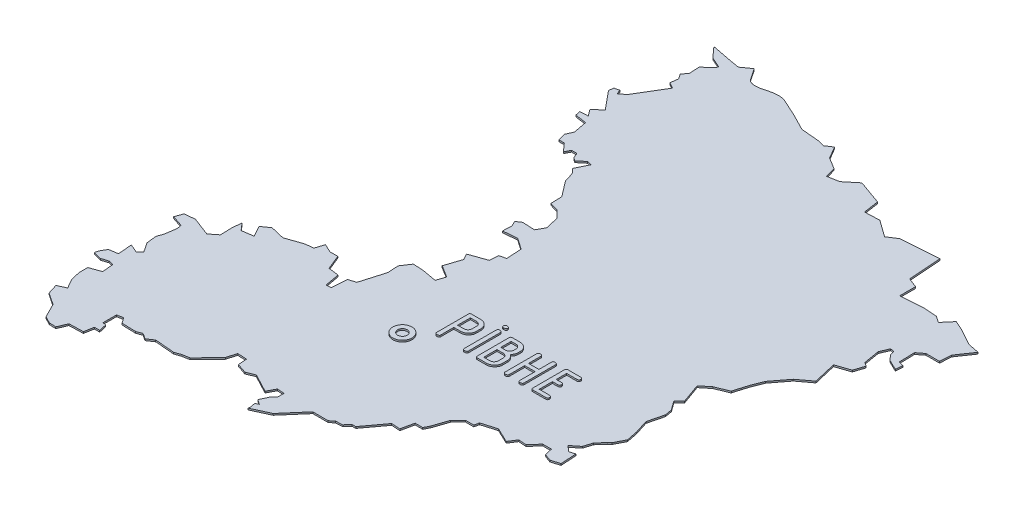
SolidWorks part; units mm, degrees
ref_plane "Спереди" through (0, 0, 0) normal (0, 0, 1) x (1, 0, 0)
ref_plane "Сверху" through (0, 0, 0) normal (0, 1, 0) x (1, 0, 0)
ref_plane "Справа" through (0, 0, 0) normal (1, 0, 0) x (0, 0, -1)
sketch "Эскиз1" plane through (0, 0, 0) normal (0, 1, 0) x (1, 0, 0)
  line B0 (-6710.873, 8600.8413) -> (-6732.9329, 8609.2792)
  line B1 (-6732.9329, 8609.2792) -> (-6738.1349, 8633.2797)
  line B2 (-6738.1349, 8633.2797) -> (-6765.3713, 8633.2797)
  line B3 (-6765.3713, 8633.2797) -> (-6790.6824, 8605.3676)
  line B4 (-6790.6824, 8605.3676) -> (-6814.6905, 8607.3209)
  line B5 (-6814.6905, 8607.3209) -> (-6830.2657, 8583.3077)
  line B6 (-6830.2657, 8583.3077) -> (-6876.3642, 8605.3676)
  line B7 (-6876.3642, 8605.3676) -> (-6922.4068, 8591.7481)
  line B8 (-6922.4068, 8591.7481) -> (-6925.6554, 8576.8332)
  line B9 (-6925.6554, 8576.8332) -> (-6951.6168, 8576.8332)
  line B10 (-6951.6168, 8576.8332) -> (-6974.9772, 8552.8125)
  line B11 (-6974.9772, 8552.8125) -> (-6990.5651, 8506.7419)
  line B12 (-6990.5651, 8506.7419) -> (-6999.003, 8489.8738)
  line B13 (-6999.003, 8489.8738) -> (-7023.0086, 8489.8738)
  line B14 (-7023.0086, 8489.8738) -> (-7031.4541, 8450.265)
  line B15 (-7031.4541, 8450.265) -> (-7058.6879, 8452.2132)
  line B16 (-7058.6879, 8452.2132) -> (-7106.7066, 8387.3365)
  line B17 (-7106.7066, 8387.3365) -> (-7118.411, 8387.3365)
  line B18 (-7118.411, 8387.3365) -> (-7132.0228, 8371.7587)
  line B19 (-7132.0228, 8371.7587) -> (-7152.7848, 8370.4735)
  line B20 (-7152.7848, 8370.4735) -> (-7166.4271, 8360.0722)
  line B21 (-7166.4271, 8360.0722) -> (-7214.4585, 8360.0722)
  line B22 (-7214.4585, 8360.0722) -> (-7272.1902, 8293.2372)
  line B23 (-7272.1902, 8293.2372) -> (-7326.0661, 8268.5788)
  line B24 (-7326.0661, 8268.5788) -> (-7324.758, 8276.3563)
  line B25 (-7324.758, 8276.3563) -> (-7328.6518, 8291.9418)
  line B26 (-7328.6518, 8291.9418) -> (-7318.2785, 8296.4706)
  line B27 (-7318.2785, 8296.4706) -> (-7333.8487, 8306.8668)
  line B28 (-7333.8487, 8306.8668) -> (-7320.2165, 8336.0844)
  line B29 (-7320.2165, 8336.0844) -> (-7309.8482, 8346.4578)
  line B30 (-7309.8482, 8346.4578) -> (-7309.8482, 8365.2665)
  line B31 (-7309.8482, 8365.2665) -> (-7331.8954, 8366.5746)
  line B32 (-7331.8954, 8366.5746) -> (-7345.5352, 8341.2584)
  line B33 (-7345.5352, 8341.2584) -> (-7403.2821, 8371.7587)
  line B34 (-7403.2821, 8371.7587) -> (-7429.2536, 8361.3803)
  line B35 (-7429.2536, 8361.3803) -> (-7459.7438, 8371.7587)
  line B36 (-7459.7438, 8371.7587) -> (-7461.692, 8399.0231)
  line B37 (-7461.692, 8399.0231) -> (-7490.9045, 8400.9611)
  line B38 (-7490.9045, 8400.9611) -> (-7499.3398, 8370.4735)
  line B39 (-7499.3398, 8370.4735) -> (-7553.8432, 8314.0067)
  line B40 (-7553.8432, 8314.0067) -> (-7575.9081, 8310.118)
  line B41 (-7575.9081, 8310.118) -> (-7594.7219, 8303.6232)
  line B42 (-7594.7219, 8303.6232) -> (-7656.3728, 8308.8099)
  line B43 (-7656.3728, 8308.8099) -> (-7676.4947, 8295.1828)
  line B44 (-7676.4947, 8295.1828) -> (-7694.0181, 8306.8668)
  line B45 (-7694.0181, 8306.8668) -> (-7710.8964, 8300.372)
  line B46 (-7710.8964, 8300.372) -> (-7755.0137, 8301.6725)
  line B47 (-7755.0137, 8301.6725) -> (-7767.3479, 8319.1858)
  line B48 (-7767.3479, 8319.1858) -> (-7786.1643, 8315.3098)
  line B49 (-7786.1643, 8315.3098) -> (-7786.1643, 8273.1153)
  line B50 (-7786.1643, 8273.1153) -> (-7775.7655, 8271.1773)
  line B51 (-7775.7655, 8271.1773) -> (-7770.5941, 8247.1743)
  line B52 (-7770.5941, 8247.1743) -> (-7787.447, 8247.1743)
  line B53 (-7787.447, 8247.1743) -> (-7792.6463, 8217.9592)
  line B54 (-7792.6463, 8217.9592) -> (-7836.7687, 8216.6663)
  line B55 (-7836.7687, 8216.6663) -> (-7849.1004, 8187.4563)
  line B56 (-7849.1004, 8187.4563) -> (-7870.5075, 8188.7593)
  line B57 (-7870.5075, 8188.7593) -> (-7891.9426, 8199.7855)
  line B58 (-7891.9426, 8199.7855) -> (-7914.0101, 8243.9231)
  line B59 (-7914.0101, 8243.9231) -> (-7951.6249, 8269.2265)
  line B60 (-7951.6249, 8269.2265) -> (-7961.3735, 8300.372)
  line B61 (-7961.3735, 8300.372) -> (-7936.0497, 8312.0459)
  line B62 (-7936.0497, 8312.0459) -> (-7952.928, 8341.2584)
  line B63 (-7952.928, 8341.2584) -> (-7960.073, 8371.7587)
  line B64 (-7960.073, 8371.7587) -> (-7960.073, 8399.0231)
  line B65 (-7960.073, 8399.0231) -> (-7925.6763, 8411.337)
  line B66 (-7925.6763, 8411.337) -> (-7928.9224, 8447.0418)
  line B67 (-7928.9224, 8447.0418) -> (-7944.5028, 8450.265)
  line B68 (-7944.5028, 8450.265) -> (-7965.2622, 8443.7982)
  line B69 (-7965.2622, 8443.7982) -> (-7990.5708, 8450.265)
  line B70 (-7990.5708, 8450.265) -> (-7987.3348, 8462.6044)
  line B71 (-7987.3348, 8462.6044) -> (-7976.936, 8480.7781)
  line B72 (-7976.936, 8480.7781) -> (-7949.6869, 8484.6897)
  line B73 (-7949.6869, 8484.6897) -> (-7952.928, 8528.8069)
  line B74 (-7952.928, 8528.8069) -> (-7925.6763, 8517.1229)
  line B75 (-7925.6763, 8517.1229) -> (-7914.0101, 8528.8069)
  line B76 (-7914.0101, 8528.8069) -> (-7934.1193, 8559.292)
  line B77 (-7934.1193, 8559.292) -> (-7938.0004, 8590.4476)
  line B78 (-7938.0004, 8590.4476) -> (-7930.8731, 8610.5695)
  line B79 (-7930.8731, 8610.5695) -> (-7925.6763, 8646.9068)
  line B80 (-7925.6763, 8646.9068) -> (-7928.9224, 8660.5364)
  line B81 (-7928.9224, 8660.5364) -> (-7963.3369, 8672.2331)
  line B82 (-7963.3369, 8672.2331) -> (-7954.8812, 8696.2209)
  line B83 (-7954.8812, 8696.2209) -> (-7922.42, 8699.4721)
  line B84 (-7922.42, 8699.4721) -> (-7864.6757, 8677.402)
  line B85 (-7864.6757, 8677.402) -> (-7840.665, 8696.2209)
  line B86 (-7840.665, 8696.2209) -> (-7841.9579, 8735.1692)
  line B87 (-7841.9579, 8735.1692) -> (-7838.727, 8762.4056)
  line B88 (-7838.727, 8762.4056) -> (-7819.9082, 8740.3635)
  line B89 (-7819.9082, 8740.3635) -> (-7784.2059, 8745.54)
  line B90 (-7784.2059, 8745.54) -> (-7803.0324, 8779.9342)
  line B91 (-7803.0324, 8779.9342) -> (-7779.0294, 8796.8049)
  line B92 (-7779.0294, 8796.8049) -> (-7734.8918, 8786.434)
  line B93 (-7734.8918, 8786.434) -> (-7683.6168, 8803.9372)
  line B94 (-7683.6168, 8803.9372) -> (-7657.6682, 8807.2036)
  line B95 (-7657.6682, 8807.2036) -> (-7649.2278, 8834.4527)
  line B96 (-7649.2278, 8834.4527) -> (-7621.9837, 8822.1109)
  line B97 (-7621.9837, 8822.1109) -> (-7597.9807, 8822.1109)
  line B98 (-7597.9807, 8822.1109) -> (-7579.1416, 8776.0429)
  line B99 (-7579.1416, 8776.0429) -> (-7546.6981, 8771.5014)
  line B100 (-7546.6981, 8771.5014) -> (-7538.2679, 8725.4309)
  line B101 (-7538.2679, 8725.4309) -> (-7523.3352, 8726.7085)
  line B102 (-7523.3352, 8726.7085) -> (-7519.4439, 8774.7399)
  line B103 (-7519.4439, 8774.7399) -> (-7497.3891, 8781.2372)
  line B104 (-7497.3891, 8781.2372) -> (-7475.3114, 8856.505)
  line B105 (-7475.3114, 8856.505) -> (-7477.2622, 8890.9042)
  line B106 (-7477.2622, 8890.9042) -> (-7458.4535, 8919.4665)
  line B107 (-7458.4535, 8919.4665) -> (-7427.2877, 8918.1661)
  line B108 (-7427.2877, 8918.1661) -> (-7379.9167, 8909.718)
  line B109 (-7379.9167, 8909.718) -> (-7370.8336, 8936.9798)
  line B110 (-7370.8336, 8936.9798) -> (-7408.4866, 8960.3529)
  line B111 (-7408.4866, 8960.3529) -> (-7391.6032, 9011.6127)
  line B112 (-7391.6032, 9011.6127) -> (-7401.9867, 9030.4264)
  line B113 (-7401.9867, 9030.4264) -> (-7348.7737, 9049.2605)
  line B114 (-7348.7737, 9049.2605) -> (-7347.4656, 9076.5097)
  line B115 (-7347.4656, 9076.5097) -> (-7326.7011, 9081.6913)
  line B116 (-7326.7011, 9081.6913) -> (-7329.9574, 9129.71)
  line B117 (-7329.9574, 9129.71) -> (-7364.3541, 9153.7257)
  line B118 (-7364.3541, 9153.7257) -> (-7408.4866, 9149.8318)
  line B119 (-7408.4866, 9149.8318) -> (-7407.1785, 9179.0317)
  line B120 (-7407.1785, 9179.0317) -> (-7415.6138, 9194.6171)
  line B121 (-7415.6138, 9194.6171) -> (-7400.0385, 9204.9854)
  line B122 (-7400.0385, 9204.9854) -> (-7361.113, 9203.0347)
  line B123 (-7361.113, 9203.0347) -> (-7347.4656, 9228.3534)
  line B124 (-7347.4656, 9228.3534) -> (-7357.2091, 9269.2499)
  line B125 (-7357.2091, 9269.2499) -> (-7381.2121, 9293.2529)
  line B126 (-7381.2121, 9293.2529) -> (-7407.1785, 9300.3802)
  line B127 (-7407.1785, 9300.3802) -> (-7408.4866, 9336.0875)
  line B128 (-7408.4866, 9336.0875) -> (-7446.0938, 9385.3965)
  line B129 (-7446.0938, 9385.3965) -> (-7454.5546, 9414.6065)
  line B130 (-7454.5546, 9414.6065) -> (-7468.1893, 9430.1589)
  line B131 (-7468.1893, 9430.1589) -> (-7449.3755, 9469.1175)
  line B132 (-7449.3755, 9469.1175) -> (-7463.63, 9472.3636)
  line B133 (-7463.63, 9472.3636) -> (-7485.6924, 9454.1848)
  line B134 (-7485.6924, 9454.1848) -> (-7495.4384, 9460.672)
  line B135 (-7495.4384, 9460.672) -> (-7502.5783, 9477.5401)
  line B136 (-7502.5783, 9477.5401) -> (-7519.4439, 9477.5401)
  line B137 (-7519.4439, 9477.5401) -> (-7527.8844, 9460.672)
  line B138 (-7527.8844, 9460.672) -> (-7550.6021, 9485.9805)
  line B139 (-7550.6021, 9485.9805) -> (-7567.4576, 9485.9805)
  line B140 (-7567.4576, 9485.9805) -> (-7573.9549, 9509.9911)
  line B141 (-7573.9549, 9509.9911) -> (-7564.2216, 9532.0587)
  line B142 (-7564.2216, 9532.0587) -> (-7572.662, 9574.8932)
  line B143 (-7572.662, 9574.8932) -> (-7608.3465, 9580.0875)
  line B144 (-7608.3465, 9580.0875) -> (-7611.5977, 9595.645)
  line B145 (-7611.5977, 9595.645) -> (-7586.2866, 9596.9455)
  line B146 (-7586.2866, 9596.9455) -> (-7601.8619, 9617.7278)
  line B147 (-7601.8619, 9617.7278) -> (-7575.9081, 9639.7877)
  line B148 (-7575.9081, 9639.7877) -> (-7623.9395, 9698.1848)
  line B149 (-7623.9395, 9698.1848) -> (-7621.9837, 9713.1048)
  line B150 (-7621.9837, 9713.1048) -> (-7606.3983, 9716.9935)
  line B151 (-7606.3983, 9716.9935) -> (-7601.8619, 9702.7213)
  line B152 (-7601.8619, 9702.7213) -> (-7583.0303, 9716.9935)
  line B153 (-7583.0303, 9716.9935) -> (-7529.8325, 9805.2636)
  line B154 (-7529.8325, 9805.2636) -> (-7548.6489, 9815.642)
  line B155 (-7548.6489, 9815.642) -> (-7545.39, 9839.6501)
  line B156 (-7545.39, 9839.6501) -> (-7555.7863, 9855.2305)
  line B157 (-7555.7863, 9855.2305) -> (-7543.4469, 9872.0885)
  line B158 (-7543.4469, 9872.0885) -> (-7545.39, 9904.5395)
  line B159 (-7545.39, 9904.5395) -> (-7524.6433, 9921.4203)
  line B160 (-7524.6433, 9921.4203) -> (-7514.2395, 9935.0525)
  line B161 (-7514.2395, 9935.0525) -> (-7548.6489, 9950.6329)
  line B162 (-7548.6489, 9950.6329) -> (-7577.8538, 9983.0712)
  line B163 (-7577.8538, 9983.0712) -> (-7514.2395, 9970.7294)
  line B164 (-7514.2395, 9970.7294) -> (-7483.7646, 9965.5401)
  line B165 (-7483.7646, 9965.5401) -> (-7454.5546, 9986.3123)
  line B166 (-7454.5546, 9986.3123) -> (-7429.2536, 9948.6898)
  line B167 (-7323.455, 9948.6898) -> (-7270.2522, 9924.6665)
  line B168 (-7270.2522, 9924.6665) -> (-7214.4585, 9896.1118)
  line B169 (-7214.4585, 9896.1118) -> (-7156.0385, 9890.9276)
  line B170 (-7156.0385, 9890.9276) -> (-7135.9243, 9885.7257)
  line B171 (-7135.9243, 9885.7257) -> (-7115.1648, 9899.3808)
  line B172 (-7115.1648, 9899.3808) -> (-7093.0872, 9861.7227)
  line B173 (-7093.0872, 9861.7227) -> (-7057.4078, 9839.6501)
  line B174 (-7057.4078, 9839.6501) -> (-7048.3146, 9807.2194)
  line B175 (-7048.3146, 9807.2194) -> (-7012.6073, 9813.6913)
  line B176 (-7012.6073, 9813.6913) -> (-6974.9772, 9844.8444)
  line B177 (-6974.9772, 9844.8444) -> (-6898.4089, 9817.5851)
  line B178 (-6898.4089, 9817.5851) -> (-6891.2791, 9769.5487)
  line B179 (-6891.2791, 9769.5487) -> (-6845.1984, 9771.5172)
  line B180 (-6845.1984, 9771.5172) -> (-6792.6331, 9733.882)
  line B181 (-6792.6331, 9733.882) -> (-6763.446, 9752.6958)
  line B182 (-6763.446, 9752.6958) -> (-6645.9786, 9761.1362)
  line B183 (-6645.9786, 9761.1362) -> (-6638.8412, 9658.6065)
  line B184 (-6638.8412, 9658.6065) -> (-6608.3256, 9646.9225)
  line B185 (-6608.3256, 9646.9225) -> (-6608.3256, 9596.9455)
  line B186 (-6608.3256, 9596.9455) -> (-6538.2623, 9602.1347)
  line B187 (-6538.2623, 9602.1347) -> (-6495.4175, 9598.8962)
  line B188 (-6495.4175, 9598.8962) -> (-6475.3033, 9585.2666)
  line B189 (-6475.3033, 9585.2666) -> (-6449.3546, 9615.7847)
  line B190 (-6449.3546, 9615.7847) -> (-6418.8492, 9602.1347)
  line B191 (-6418.8492, 9602.1347) -> (-6367.5895, 9573.5851)
  line B192 (-6367.5895, 9573.5851) -> (-6331.8771, 9566.4553)
  line B193 (-6331.8771, 9566.4553) -> (-6365.6388, 9517.126)
  line B194 (-6365.6388, 9517.126) -> (-6367.5895, 9481.4517)
  line B195 (-6367.5895, 9481.4517) -> (-6410.4139, 9481.4517)
  line B196 (-6410.4139, 9481.4517) -> (-6430.5307, 9465.8536)
  line B197 (-6430.5307, 9465.8536) -> (-6429.2328, 9416.5522)
  line B198 (-6429.2328, 9416.5522) -> (-6413.66, 9412.6507)
  line B199 (-6413.66, 9412.6507) -> (-6415.5904, 9390.5857)
  line B200 (-6415.5904, 9390.5857) -> (-6448.0465, 9406.1432)
  line B201 (-6448.0465, 9406.1432) -> (-6462.9792, 9423.0419)
  line B202 (-6462.9792, 9423.0419) -> (-6466.8679, 9436.6512)
  line B203 (-6466.8679, 9436.6512) -> (-6478.5621, 9438.6171)
  line B204 (-6478.5621, 9438.6171) -> (-6490.2283, 9411.3553)
  line B205 (-6490.2283, 9411.3553) -> (-6481.8006, 9361.3808)
  line B206 (-6481.8006, 9361.3808) -> (-6470.1191, 9352.9582)
  line B207 (-6470.1191, 9352.9582) -> (-6480.4925, 9320.5071)
  line B208 (-6480.4925, 9320.5071) -> (-6524.6225, 9305.5796)
  line B209 (-6524.6225, 9305.5796) -> (-6507.7467, 9233.5477)
  line B210 (-6507.7467, 9233.5477) -> (-6548.6509, 9203.0347)
  line B211 (-6548.6509, 9203.0347) -> (-6586.2835, 9153.7257)
  line B212 (-6613.5148, 9073.2686) -> (-6654.4139, 9056.3725)
  line B213 (-6654.4139, 9056.3725) -> (-6681.6681, 9034.3126)
  line B214 (-6681.6681, 9034.3126) -> (-6659.5981, 8972.6846)
  line B215 (-6659.5981, 8972.6846) -> (-6676.4789, 8955.8012)
  line B216 (-6676.4789, 8955.8012) -> (-6656.3519, 8927.9019)
  line B217 (-6656.3519, 8927.9019) -> (-6652.4581, 8905.842)
  line B218 (-6652.4581, 8905.842) -> (-6664.7873, 8856.505)
  line B219 (-6664.7873, 8856.505) -> (-6651.1627, 8813.6933)
  line B220 (-6651.1627, 8813.6933) -> (-6644.0279, 8777.9962)
  line B221 (-6644.0279, 8777.9962) -> (-6660.9036, 8745.54)
  line B222 (-6660.9036, 8745.54) -> (-6668.0385, 8739.0554)
  line B223 (-6668.0385, 8739.0554) -> (-6688.803, 8716.3554)
  line B224 (-6688.803, 8716.3554) -> (-6697.2358, 8689.086)
  line B225 (-6697.2358, 8689.086) -> (-6722.5443, 8668.9768)
  line B226 (-6722.5443, 8668.9768) -> (-6703.728, 8653.3914)
  line B227 (-6703.728, 8653.3914) -> (-6686.8573, 8658.5755)
  line B228 (-6686.8573, 8658.5755) -> (-6683.6188, 8609.2792)
  line B229 (-6683.6188, 8609.2792) -> (-6710.873, 8600.8413)
  spline B230 degree 2 poles (-7429.2536, 9948.6898) (-7413.6809, 9935.0525) (-7379.9167, 9945.436) knots 0.710638 0.710638 0.710638 0.714894 0.714894 0.714894
  spline B231 degree 2 poles (-7379.9167, 9945.436) (-7345.5352, 9955.8145) (-7323.455, 9948.6898) knots 0.714894 0.714894 0.714894 0.719149 0.719149 0.719149
  spline B232 degree 2 poles (-6586.2835, 9153.7257) (-6603.144, 9112.8317) (-6606.3774, 9098.567) knots 0.910638 0.910638 0.910638 0.914894 0.914894 0.914894
  spline B233 degree 2 poles (-6606.3774, 9098.567) (-6610.2713, 9084.9425) (-6613.5148, 9073.2686) knots 0.914894 0.914894 0.914894 0.919149 0.919149 0.919149
sketch_block_instance "Блок24-1"
sketch_block "Блок24"
extrude "Бобышка-Вытянуть1" add sketch "Эскиз1" along normal blind 5 contours B233 B232 B211 B210 B209 B208 B207 B206 B205 B204 B203 B202 B201 B200 B199 B198 B197 B196 B195 B194 B193 B192 B191 B190 B189 B188 B187 B186 B185 B184 B183 B182 B181 B180 B179 B178 B177 B176 B175 B174 B173 B172 B171 B170 B169 B168 B167 B231 B230 B166 B165 region at (-7162.1609, 0, -9093.4007)
sketch "Эскиз2" plane through (0, 0, 0) normal (0, 1, 0) x (1, 0, 0)
  line L0 (-7238.4037, 8759.9817) -> (-6783.7704, 8759.9817) construction
  circle A0 centre (-7284.4879, 8711.5513) radius 15
  circle A1 centre (-7284.4879, 8711.5513) radius 30
  text T0 "<b>РІВНЕ</b>" font "GOST Type AU" height 110
  dimension "D1" = 30
  dimension "D2" = 60
extrude "Бобышка-Вытянуть2" add sketch "Эскиз2" along normal blind 10
scale "Масштаб1" scale about centroid uniform scaling yes scale factor 0.05
